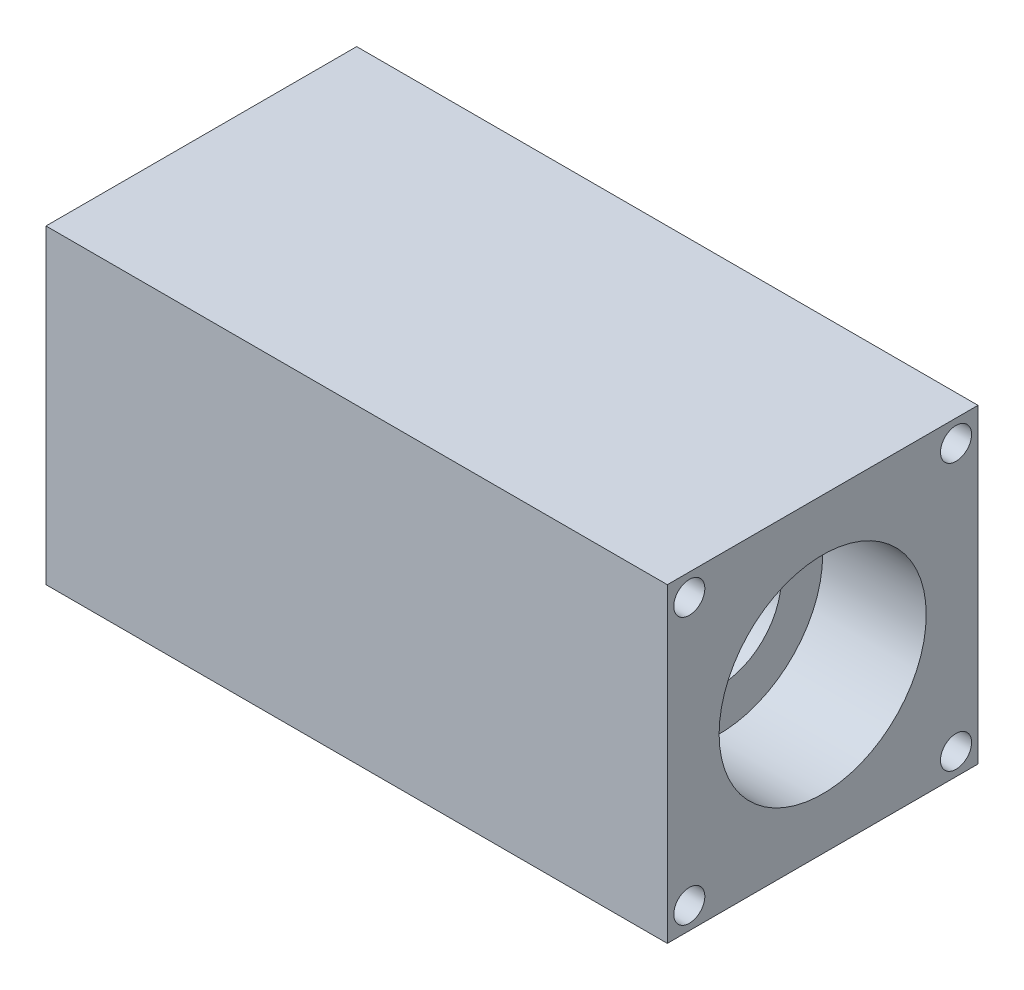
SolidWorks part; units mm, degrees
ref_plane "Front Plane" through (0, 0, 0) normal (0, 0, 1) x (1, 0, 0)
ref_plane "Top Plane" through (0, 0, 0) normal (0, 1, 0) x (1, 0, 0)
ref_plane "Right Plane" through (0, 0, 0) normal (1, 0, 0) x (0, 0, -1)
sketch "Sketch1" plane through (0, 0, 0) normal (0, 1, 0) x (1, 0, 0)
  line L0 (0, 15) -> (60, 15) construction
  line L1 (0, 30) -> (60, 30)
  line L2 (0, 30) -> (0, 0)
  line L3 (0, 0) -> (60, 0)
  line L4 (60, 30) -> (60, 0)
  line L5 (30, 30) -> (30, 0) construction
  dimension "D1" = 60
  dimension "D2" = 30
extrude "Boss-Extrude1" add sketch "Sketch1" along normal blind 30
sketch "Sketch2" plane through (0, 0, 0) normal (-1, 0, 0) x (0, 0, 1)
  line L0 (-15, 30) -> (-15, 0) construction
  line L1 (-30, 30) -> (0, 30) construction
  line L2 (-30, 0) -> (0, 0) construction
  line L3 (-30, 15) -> (0, 15) construction
  line L4 (-30, 30) -> (-30, 0) construction
  line L5 (0, 30) -> (0, 0) construction
  circle A0 centre (-15, 15) radius 6
  circle A1 centre (-15, 15) radius 10
  dimension "D1" = 12
  dimension "D2" = 20
extrude "Cut-Extrude1" cut sketch "Sketch2" against normal through all contours A0
extrude "Cut-Extrude2" cut sketch "Sketch2<4>" against normal blind 10
sketch "Sketch2<4>" plane through (0, 0, 0) normal (-1, 0, 0) x (0, 0, 1) same geometry as "Sketch2"
ref_plane "Plane1" through (30, 0, 0) normal (-1, 0, 0) x (0, 0, 1)
mirror "Mirror1" about plane through (30, 0, 0) normal (-1, 0, 0) of "Cut-Extrude2"
sketch "Sketch5" plane through (0, 0, 0) normal (-1, 0, 0) x (0, 0, 1)
  line L0 (-30, 30) -> (0, 0) construction
  line L1 (-30, 0) -> (0, 30) construction
  line L2 (-30, 15) -> (0, 15) construction
  line L3 (-30, 30) -> (-30, 0) construction
  line L4 (0, 30) -> (0, 0) construction
  circle A0 centre (-27.8787, 27.8787) radius 1.5
  circle A1 centre (-2.1213, 2.1213) radius 1.5
  circle A2 centre (-2.1213, 27.8787) radius 1.5
  circle A3 centre (-27.8787, 2.1213) radius 1.5
  dimension "D2" = 3
  dimension "D1" = 3
extrude "Cut-Extrude4" cut sketch "Sketch5" against normal blind 10
mirror "Mirror2" about plane through (30, 0, 0) normal (-1, 0, 0) of "Cut-Extrude4"
sketch "Sketch6" plane through (0, 0, -30) normal (0, 0, -1) x (-1, 0, 0)
  line L0 (-60, 30) -> (0, 0) construction
  line L1 (-60, 0) -> (0, 30) construction
  circle A0 centre (-30, 15) radius 6.5944
  circle A1 centre (-30, 15) radius 9.3026
  dimension "D1" = 13.1888
  dimension "D2" = 18.6052
extrude "Cut-Extrude5" cut sketch "Sketch6" against normal blind 15 contours A0
equation "\"WIDTH_CENTRE\" = 0.06m"
equation "\"LENGTH_CENTRE\"= 0.03m"
equation "\"D1@Sketch1\"=\"WIDTH_CENTRE\""
equation "\"D2@Sketch1\"=\"LENGTH_CENTRE\""
equation "\"HEIGHT_CENTRE\"=0.03"
equation "\"D1@Boss-Extrude1\"=\"HEIGHT_CENTRE\""
equation "\"SIDE_SHAFT_DIAM\"= 12mm"
equation "\"D1@Sketch2\"=\"SIDE_SHAFT_DIAM\""
equation "\"OUTER_DIAM_SIDE_BEARINGS\" = 0.02"
equation "\"D2@Sketch2\"=\"OUTER_DIAM_SIDE_BEARINGS\""
equation "\"SIDE_BEARING_WIDTH\" = 0.01"
equation "\"D1@Cut-Extrude2\"= \"SIDE_BEARING_WIDTH\""
equation "\"SIDE_INSERT_EDGE\"=0.003"
equation "\"D1@Sketch5\"=\"SIDE_INSERT_EDGE\""
equation "\"SIDE_INSERT_DIAM\"= 0.003"
equation "\"D2@Sketch5\"=\"SIDE_INSERT_DIAM\""
equation "\"SIDE_INSERT_DEPTH\"=0.01"
equation "\"D1@Cut-Extrude4\"=\"SIDE_INSERT_DEPTH\""
equation "\"CENTRE_SHAFT_DIAM\"=0.0131888"
equation "\"D1@Sketch6\"=\"CENTRE_SHAFT_DIAM\""
equation "\"OUTER_DIAM_CENTRE_BEARINGS\"=0.0186052"
equation "\"D2@Sketch6\"=\"OUTER_DIAM_CENTRE_BEARINGS\""
equation "\"D1@Cut-Extrude5\"=\"LENGTH_CENTRE\"*0.5"
